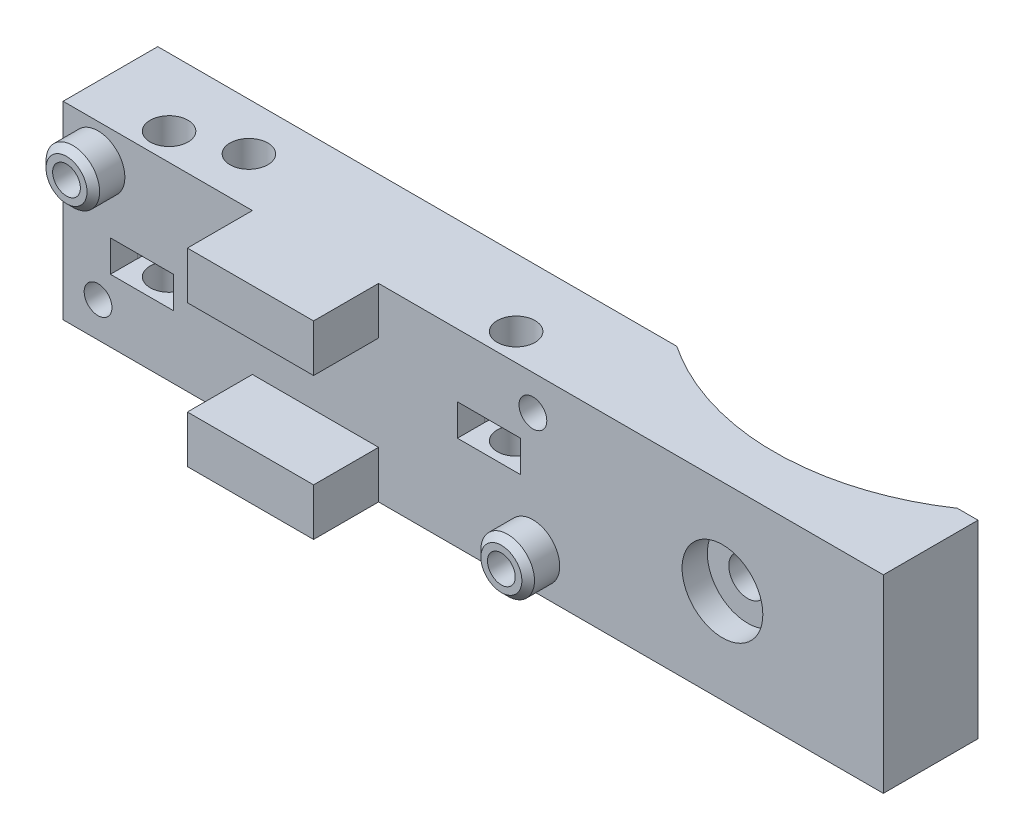
SolidWorks part; units mm, degrees
ref_plane "Front Plane" through (0, 0, 0) normal (0, 0, 1) x (1, 0, 0)
ref_plane "Top Plane" through (0, 0, 0) normal (0, 1, 0) x (1, 0, 0)
ref_plane "Right Plane" through (0, 0, 0) normal (1, 0, 0) x (0, 0, -1)
sketch "Sketch1" plane through (0, 0, 0) normal (0, 0, 1) x (1, 0, 0)
  line L1 (-25.4, 9.525) -> (25.4, 9.525)
  line L2 (-25.4, 9.525) -> (-25.4, -9.525)
  line L3 (-25.4, -9.525) -> (25.4, -9.525)
  line L4 (25.4, 9.525) -> (25.4, -9.525)
  line L5 (-25.4, 9.525) -> (25.4, -9.525) construction
  line L6 (-25.4, -9.525) -> (25.4, 9.525) construction
  point P0 (0, 0)
  dimension "D1" = 50.8
  dimension "D2" = 19.05
extrude "Boss-Extrude1" add sketch "Sketch1" along normal blind 9.525
sketch "Sketch2" plane through (0, 0, 9.525) normal (0, 0, 1) x (1, 0, 0)
  line L0 (-21.8821, -6.0071) -> (-21.8821, 6.0071) construction
  line L1 (-21.8821, 6.0071) -> (-25.4, 6.0071) construction
  line L2 (-25.4, 9.525) -> (-25.4, -9.525) construction
  line L3 (-21.8821, 6.0071) -> (-21.8821, 9.525) construction
  line L4 (25.4, 9.525) -> (-25.4, 9.525) construction
  line L5 (0, -9.525) -> (0, 9.525) construction
  circle A0 centre (-21.8821, -6.0071) radius 1.397
  circle A1 centre (-21.8821, 6.0071) radius 1.397
  circle A2 centre (21.8821, -6.0071) radius 1.397
  circle A3 centre (21.8821, 6.0071) radius 1.397
  point P4 (-21.8821, 0)
  point P16 (0, 0)
  dimension "D1" = 2.794
  dimension "D2" = 2.794
  dimension "D3" = 12.0142
extrude "Cut-Extrude1" cut sketch "Sketch2" against normal through all
sketch "Sketch5" plane through (0, 9.525, 0) normal (0, 1, 0) x (1, 0, 0)
  line L0 (-25.4, -9.525) -> (-25.4, 0) construction
  line L1 (25.4, 0) -> (-25.4, 0) construction
  line L2 (0, 0) -> (0, -9.525) construction
  line L3 (25.4, -9.525) -> (-25.4, -9.525) construction
  circle A0 centre (-17.4625, -6.7945) radius 1.905
  circle A1 centre (17.4625, -6.7945) radius 1.905
  dimension "D1" = 7.9375
  dimension "D2" = 3.81
  dimension "D3" = 6.7945
extrude "Cut-Extrude3" cut sketch "Sketch5" against normal through all
sketch "Sketch3" plane through (0, 9.525, 0) normal (0, 1, 0) x (1, 0, 0)
  line L0 (-20.6375, -6.7945) -> (-20.6375, -9.525)
  line L1 (25.4, -9.525) -> (-25.4, -9.525) construction
  line L2 (-14.2875, -6.7945) -> (-14.2875, -9.525)
  line L3 (-14.2875, -9.525) -> (-20.6375, -9.525)
  arc A0 (-14.2875, -6.7945) -> (-20.6375, -6.7945) centre (-17.4625, -6.7945) ccw
  circle A1 centre (-17.4625, -6.7945) radius 1.905 construction
  dimension "D1" = 3.175
extrude "Cut-Extrude2" cut sketch "Sketch3" against normal blind 3.175 from offset 9.525 offset against normal yes
sketch "Sketch6" plane through (0, 9.525, 0) normal (0, 1, 0) x (1, 0, 0)
  line L0 (14.2875, -6.7945) -> (14.2875, -9.525)
  line L1 (25.4, -9.525) -> (-25.4, -9.525) construction
  line L2 (20.6375, -6.7945) -> (20.6375, -9.525)
  line L3 (14.2875, -9.525) -> (20.6375, -9.525)
  arc A0 (20.6375, -6.7945) -> (14.2875, -6.7945) centre (17.4625, -6.7945) ccw
  dimension "D1" = 6.35
extrude "Cut-Extrude4" cut sketch "Sketch6" against normal blind 3.175 from offset 6.35 offset against normal yes
sketch "Sketch7" plane through (0, 0, 9.525) normal (0, 0, 1) x (1, 0, 0)
  circle A0 centre (-21.8821, 6.0071) radius 2.6987
  circle A1 centre (-21.8821, 6.0071) radius 1.397
  circle A2 centre (21.8821, -6.0071) radius 2.6987
  circle A3 centre (21.8821, -6.0071) radius 1.397
  circle A5 centre (-21.8821, 6.0071) radius 1.397 construction
  circle A6 centre (21.8821, -6.0071) radius 1.397 construction
  dimension "D1" = 5.3975
  dimension "D2" = 5.3975
extrude "Boss-Extrude2" add sketch "Sketch7" along normal blind 3.175
chamfer "Chamfer1" distance 0.635 angle 45 2 edges at (-19.1833, 6.0071, 12.7) (24.5808, -6.0071, 12.7)
sketch "Sketch9" plane through (0, 0, 9.525) normal (0, 0, 1) x (1, 0, 0)
sketch "Sketch10" plane through (0, 0, 9.525) normal (0, 0, 1) x (1, 0, 0)
  line L0 (25.4, 9.525) -> (-25.4, 9.525) construction
  line L1 (-6.35, 9.525) -> (6.35, 9.525)
  line L2 (-6.35, 9.525) -> (-6.35, 4.7625)
  line L3 (-6.35, 4.7625) -> (6.35, 4.7625)
  line L4 (6.35, 9.525) -> (6.35, 4.7625)
  line L5 (-25.4, -9.525) -> (25.4, -9.525) construction
  line L6 (-6.35, -9.525) -> (6.35, -9.525)
  line L7 (-6.35, -9.525) -> (-6.35, -4.7625)
  line L8 (-6.35, -4.7625) -> (6.35, -4.7625)
  line L9 (6.35, -9.525) -> (6.35, -4.7625)
  point P6 (0, 4.7625)
  point P14 (0, -4.7625)
  dimension "D1" = 12.7
  dimension "D2" = 4.7625
  dimension "D3" = 4.7625
  dimension "D4" = 12.7
extrude "Boss-Extrude4" add sketch "Sketch10" along normal blind 6.5405
sketch "Sketch24" plane through (0, 0, 0) normal (0, 0, -1) x (-1, 0, 0)
  line L0 (25.4, -9.525) -> (-25.4, -9.525) construction
  line L1 (-25.4, 9.525) -> (-57.15, 9.525)
  line L2 (-25.4, 9.525) -> (-25.4, -9.525)
  line L3 (-25.4, -9.525) -> (-57.15, -9.525)
  line L4 (-57.15, 9.525) -> (-57.15, -9.525)
  dimension "D1" = 31.75
extrude "Boss-Extrude5" add sketch "Sketch24" against normal up to surface (9.525 mm away) up to face at (-19.1833, 6.0071, 9.525)
sketch "Sketch25" plane through (0, 9.525, 0) normal (0, 1, 0) x (1, 0, 0)
  line L0 (-25.4, -9.525) -> (-25.4, 0) construction
  circle A0 centre (-11.4633, -4.7625) radius 1.905
  point P4 (-25.4, -4.7625)
  point P5 (-9.5742, -4.739)
  point P6 (-11.8915, -4.7625)
  point P7 (0, 0)
  point P8 (-11.4633, -4.7625)
  dimension "D1" = 3.81
extrude "Cut-Extrude12" cut sketch "Sketch25" against normal through all
ref_plane "Plane2" through (0, 0, 0) normal (0, 1, 0) x (1, 0, 0)
sketch "Sketch27" plane through (0, 0, 0) normal (0, 1, 0) x (1, 0, 0)
  line L0 (2.8575, 84.0793) -> (84.6123, 84.0793) construction
  circle A0 centre (40.9575, 20.5793) radius 25.4
  dimension "D1" = 50.8
  dimension "D2" = 40.9575
  dimension "D3" = 63.5
revolve "Cut-Revolve2" cut sketch "Sketch27" angle 360 about L0
sketch "Sketch28" plane through (0, 0, 9.525) normal (0, 0, 1) x (1, 0, 0)
  line L0 (8.836, 0) -> (-8.836, 0) construction
  circle A0 centre (40.9575, 0) radius 1.905
  dimension "D1" = 40.9575
  dimension "D2" = 3.81
extrude "Cut-Extrude13" cut sketch "Sketch28" against normal through all contours A0
sketch "Sketch29" plane through (0, 0, 9.525) normal (0, 0, 1) x (1, 0, 0)
  circle A0 centre (40.9575, 0) radius 4.064
  dimension "D1" = 8.128
extrude "Cut-Extrude14" cut sketch "Sketch29" against normal blind 2.54
